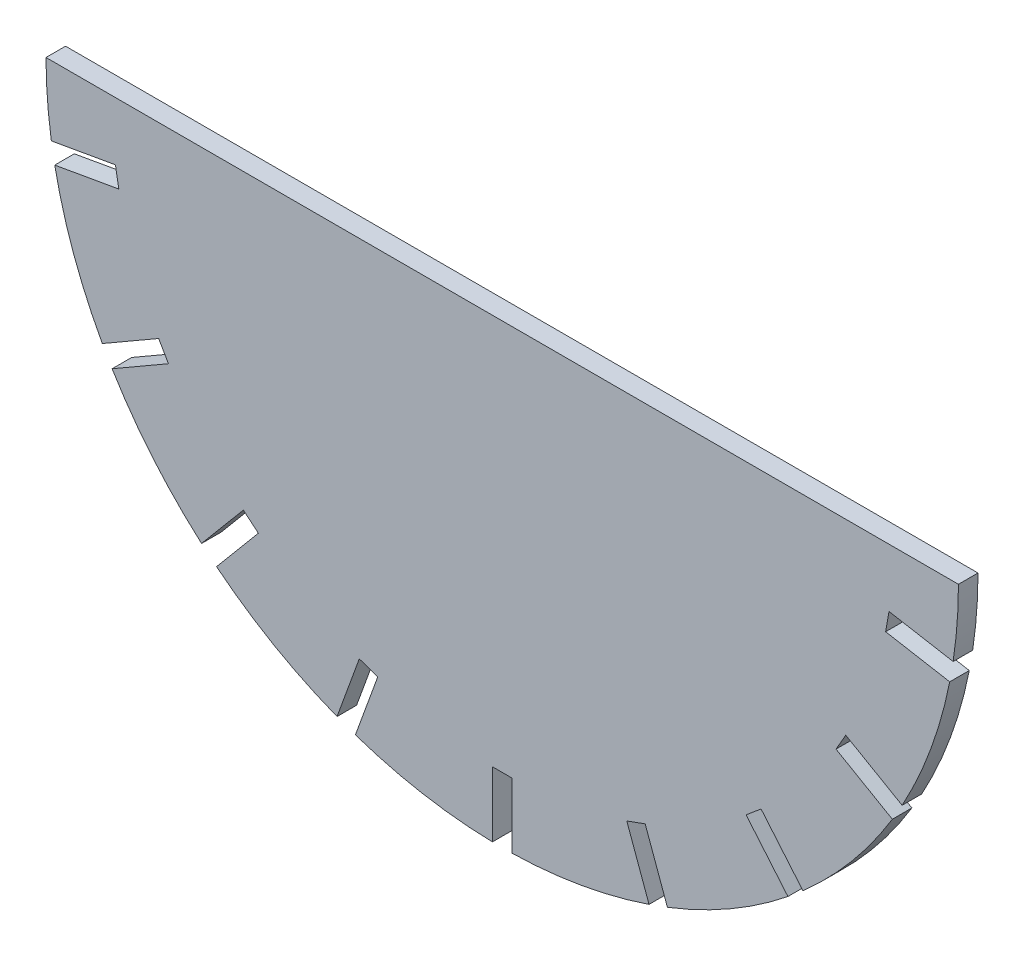
SolidWorks part; units mm, degrees
ref_plane "Front Plane" through (0, 0, 0) normal (0, 0, 1) x (1, 0, 0)
ref_plane "Top Plane" through (0, 0, 0) normal (0, 1, 0) x (1, 0, 0)
ref_plane "Right Plane" through (0, 0, 0) normal (1, 0, 0) x (0, 0, -1)
sketch "Sketch4" plane through (0, 0, 0) normal (0, 0, 1) x (1, 0, 0)
  line L1 (70, 0) -> (-70, 0)
  arc A0 (-70, 0) -> (70, 0) centre (0, 0) ccw
  dimension "D1" = 140
extrude "Boss-Extrude1" add sketch "Sketch4" along normal blind 3
sketch "Sketch5" plane through (0, 0, 0) normal (0, 0, 1) x (1, 0, 0)
  line L1 (-1.5, -60) -> (-1.5, -70)
  line L2 (-1.5, -60) -> (1.5, -60)
  line L4 (-1.5, -70) -> (1.5, -70)
  line L5 (1.5, -60) -> (1.5, -70)
extrude "Cut-Extrude2" cut sketch "Sketch5" along normal through all
ref_axis "Axis1" through (0, 0, 3) along (0, 0, -1)
pattern_circular "CirPattern1" count 5 every 20 about axis through (0, 0, 3) along (0, 0, -1) of "Cut-Extrude2" other way count 5
